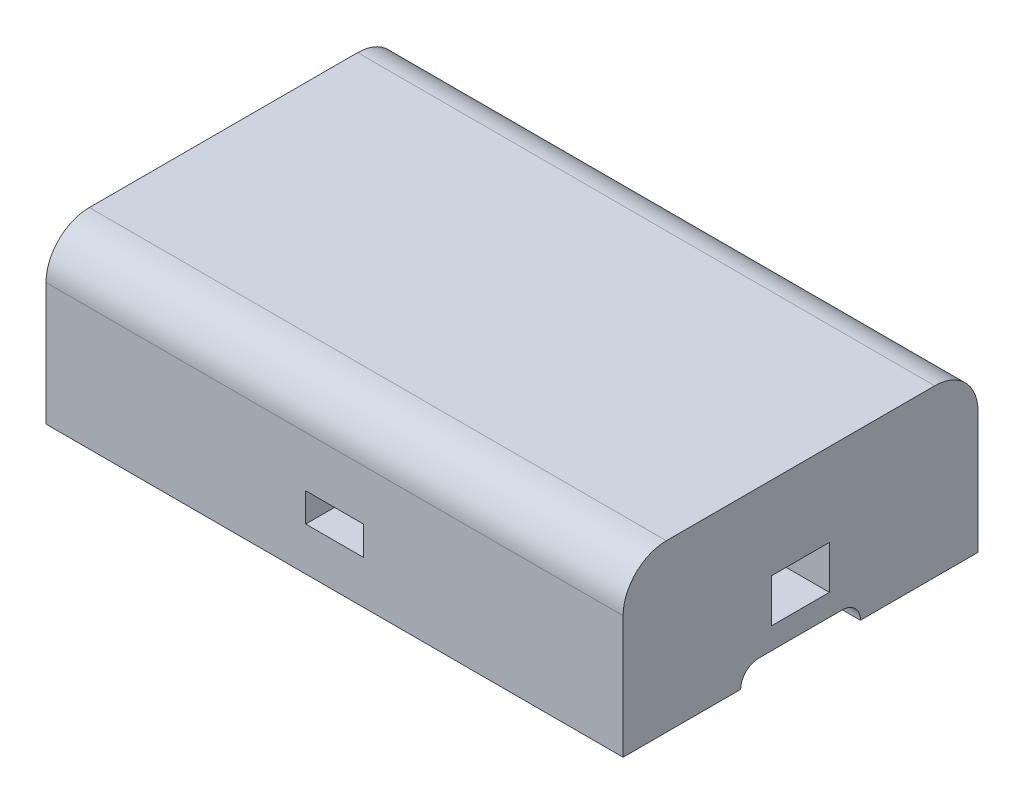
SolidWorks part; units mm, degrees
ref_plane "Front Plane" through (0, 0, 0) normal (0, 0, 1) x (1, 0, 0)
ref_plane "Top Plane" through (0, 0, 0) normal (0, 1, 0) x (1, 0, 0)
ref_plane "Right Plane" through (0, 0, 0) normal (1, 0, 0) x (0, 0, -1)
sketch "Sketch1" plane through (0, 0, 0) normal (0, 1, 0) x (1, 0, 0)
  line L1 (-17, 9.3) -> (17, 9.3)
  line L2 (-17, 9.3) -> (-17, -9.3)
  line L3 (-17, -9.3) -> (17, -9.3)
  line L4 (17, 9.3) -> (17, -9.3)
  line L5 (-17, 9.3) -> (17, -9.3) construction
  line L6 (-17, -9.3) -> (17, 9.3) construction
  line L7 (-20, 12.3) -> (20, 12.3)
  line L8 (-20, 12.3) -> (-20, -12.3)
  line L9 (-20, -12.3) -> (20, -12.3)
  line L10 (20, 12.3) -> (20, -12.3)
  line L11 (-20, 12.3) -> (20, -12.3) construction
  line L12 (-20, -12.3) -> (20, 12.3) construction
  point P0 (0, 0)
  point P6 (0, 0)
  dimension "D1" = 34
  dimension "D2" = 18.6
  dimension "D3" = 3
  dimension "D4" = 3
extrude "Boss-Extrude1" add sketch "Sketch1" along normal blind 14
ref_plane "Plane1" through (0, 5.5, 0) normal (0, -1, 0) x (-1, 0, 0)
sketch "Sketch3" plane through (20, 0, 0) normal (1, 0, 0) x (0, 0, -1)
  line L0 (-13.53, 5.5) -> (13.53, 5.5) construction
  line L1 (-2.9, 5.5) -> (2.9, 5.5) construction
  line L2 (-2.9, 6.75) -> (2.9, 6.75)
  line L3 (-2.9, 4.25) -> (2.9, 4.25)
  line L5 (-4.15, 6.75) -> (4.15, 6.75)
  line L6 (-4.15, 6.75) -> (-4.15, 4.25)
  line L7 (-4.15, 4.25) -> (4.15, 4.25)
  line L8 (4.15, 6.75) -> (4.15, 4.25)
  line L9 (-4.15, 6.75) -> (4.15, 4.25) construction
  line L10 (-4.15, 4.25) -> (4.15, 6.75) construction
  arc A0 (-2.9, 6.75) -> (-2.9, 4.25) centre (-2.9, 5.5) ccw
  arc A1 (2.9, 4.25) -> (2.9, 6.75) centre (2.9, 5.5) ccw
  point P4 (0, 5.5)
  point P9 (0, 5.5)
  dimension "D4" = 1.25
  dimension "D1" = 8.3
  dimension "D2" = 2.5
  dimension "D3" = 0
  dimension "D5" = 0
extrude "Cut-Extrude1" cut sketch "Sketch3" against normal blind 10 contours A1 L2 A0 L3 region at (20, 5.5, 0)
split "Split1" trim tools "Plane1" bodies to split 102 resulting bodies 103 104
sketch "Sketch5" plane through (20, 0, 0) normal (1, 0, 0) x (0, 0, -1)
  line L0 (-2.9, 6.75) -> (2.9, 6.75) construction
  line L1 (-2, 11.25) -> (2, 11.25)
  line L2 (-2, 11.25) -> (-2, 8.25)
  line L3 (-2, 8.25) -> (2, 8.25)
  line L4 (2, 11.25) -> (2, 8.25)
  line L5 (-2, 11.25) -> (2, 8.25) construction
  line L6 (-2, 8.25) -> (2, 11.25) construction
  point P0 (0, 9.75)
  dimension "D1" = 3
  dimension "D2" = 4
  dimension "D3" = 0
  dimension "D4" = 1.5
extrude "Cut-Extrude2" cut sketch "Sketch5" against normal blind 10
sketch "Sketch6" plane through (20, 0, 0) normal (1, 0, 0) x (0, 0, -1)
  line L0 (-12.3, 14) -> (12.3, 14) construction
  line L1 (-9.3, 17) -> (9.3, 17)
  line L2 (-12.3, 14) -> (12.3, 14)
  arc A0 (-12.3, 14) -> (-9.3, 17) centre (-9.3, 14) cw
  arc A1 (12.3, 14) -> (9.3, 17) centre (9.3, 14) ccw
  dimension "D3" = 3
  dimension "D1" = 3
  dimension "D2" = 3
extrude "Boss-Extrude2" add sketch "Sketch6" against normal blind 40 contours L1 A1 L2 A0
sketch "Sketch7" plane through (-20, 0, 0) normal (-1, 0, 0) x (0, 0, 1)
  line L0 (-12.3, 0) -> (12.3, 0) construction
  line L1 (12.3, 5.5) -> (12.3, 0) construction
  line L2 (-12.3, 5.5) -> (-12.3, 0) construction
  line L3 (-9.3, -3) -> (9.3, -3)
  line L4 (12.3, 0) -> (-12.3, 0)
  arc A0 (-12.3, 0) -> (-9.3, -3) centre (-9.3, 0) ccw
  arc A1 (12.3, 0) -> (9.3, -3) centre (9.3, 0) cw
  dimension "D1" = 3
  dimension "D2" = 3
  dimension "D3" = 0
  dimension "D4" = 0
extrude "Boss-Extrude3" add sketch "Sketch7" against normal blind 40
sketch "Sketch8" plane through (0, 0, 12.3) normal (0, 0, 1) x (1, 0, 0)
  line L1 (2, 0.5) -> (-2, 0.5)
  line L2 (2, 0.5) -> (2, 12.5)
  line L3 (2, 12.5) -> (-2, 12.5)
  line L4 (-2, 0.5) -> (-2, 12.5)
  line L5 (2, 0.5) -> (-2, 12.5) construction
  line L6 (2, 12.5) -> (-2, 0.5) construction
  line L7 (20, 5.5) -> (-20, 5.5) construction
  point P0 (0, 6.5)
  point P7 (0, 5.5)
  point P8 (0, 0)
  dimension "D1" = 4
  dimension "D2" = 12
  dimension "D3" = 5
extrude "Boss-Extrude4" add sketch "Sketch8" along normal blind 1
fillet "Fillet4" radius 21 1 edges at (0, 0.5, 13.3)
sketch "Sketch10" plane through (0, 0, 12.3) normal (0, 0, -1) x (-1, 0, 0)
  line L0 (2, 12.5) -> (2, 5.5) construction
  line L1 (-2, 10.5) -> (2, 10.5)
  line L2 (-2, 10.5) -> (-2, 8.5)
  line L3 (-2, 8.5) -> (2, 8.5)
  line L4 (2, 10.5) -> (2, 8.5)
  line L5 (-2, 10.5) -> (2, 8.5) construction
  line L6 (-2, 8.5) -> (2, 10.5) construction
  line L8 (-2, 12.5) -> (2, 12.5) construction
  point P0 (0, 9.5)
  dimension "D1" = 2
  dimension "D2" = 2
extrude "Boss-Extrude6" add sketch "Sketch10" along normal blind 1
sketch "Sketch13" plane through (0, 0, -12.3) normal (0, 0, -1) x (-1, 0, 0)
  line L0 (20, 5.5) -> (-20, 5.5) construction
  line L1 (-13, 5.5) -> (-11, 5.5)
  line L2 (-13, 5.5) -> (-13, 8.5)
  line L3 (-13, 8.5) -> (-11, 8.5)
  line L4 (-11, 5.5) -> (-11, 8.5)
  line L5 (0, 0) -> (0, -9.2638) construction
  line L6 (11, 5.5) -> (11, 8.5)
  line L7 (13, 8.5) -> (11, 8.5)
  line L8 (13, 5.5) -> (13, 8.5)
  line L9 (13, 5.5) -> (11, 5.5)
  line L10 (-20, 5.5) -> (-20, 0) construction
  dimension "D1" = 3
  dimension "D2" = 2
  dimension "D3" = 7
extrude "Boss-Extrude7" add sketch "Sketch13" against normal blind 1
sketch "Sketch14" plane through (0, 0, -11.3) normal (0, 0, 1) x (1, 0, 0)
  line L0 (-11, 8.5) -> (-11, 5.5) construction
  line L1 (-13, 8.5) -> (-11, 8.5)
  line L2 (-13, 8.5) -> (-13, 7)
  line L3 (-13, 7) -> (-11, 7)
  line L4 (-11, 8.5) -> (-11, 7)
  line L5 (13, 8.5) -> (13, 5.5) construction
  line L6 (11, 8.5) -> (13, 8.5)
  line L7 (11, 8.5) -> (11, 7)
  line L8 (11, 7) -> (13, 7)
  line L9 (13, 8.5) -> (13, 7)
  dimension "D1" = 1.5
  dimension "D2" = 1.5
extrude "Boss-Extrude9" add sketch "Sketch14" along normal blind 1 contours L8 L9 L6 L7
extrude "Boss-Extrude10" add sketch "Sketch14<4>" along normal blind 1
sketch "Sketch14<4>" plane through (0, 0, -11.3) normal (0, 0, 1) x (1, 0, 0) same geometry as "Sketch14"
sketch "Sketch15" plane through (13, 0, 0) normal (1, 0, 0) x (0, 0, -1)
  line L0 (10.3, 7) -> (11.3, 8.5)
  line L1 (10.3, 8.5) -> (12.3, 8.5) construction
  line L2 (11.3, 8.5) -> (10.3, 8.5)
  line L3 (10.3, 8.5) -> (10.3, 7)
extrude "Cut-Extrude5" cut sketch "Sketch15" against normal blind 28
sketch "Sketch16" plane through (2, 0, 0) normal (1, 0, 0) x (0, 0, -1)
  line L0 (-13.3, 12.5) -> (-12.3, 10.5)
  line L1 (-12.3, 10.5) -> (-12.3, 12.5)
  line L2 (-12.3, 12.5) -> (-13.3, 12.5)
extrude "Cut-Extrude6" cut sketch "Sketch16" against normal blind 28
fillet "Fillet7" radius 0.25 1 edges at (0, 12.5, 13.3)
sketch "Sketch18" plane through (0, 0, 0) normal (0, 1, 0) x (1, 0, 0)
  line L1 (-17, 9.3) -> (17, 9.3)
  line L2 (-17, 9.3) -> (-17, -9.3)
  line L3 (-17, -9.3) -> (17, -9.3)
  line L4 (17, 9.3) -> (17, -9.3)
extrude "Boss-Extrude11" add sketch "Sketch18" along normal blind 1.25
sketch "Sketch19" plane through (-2, 0, 0) normal (-1, 0, 0) x (0, 0, 1)
  line L0 (12.3, 10.5) -> (11.3, 8.5)
  line L1 (11.3, 8.5) -> (11.3, 10.5)
  line L2 (11.3, 10.5) -> (12.3, 10.5)
extrude "Cut-Extrude7" cut sketch "Sketch19" against normal blind 5.25
combine bodies "Combine3" operation type subtract main body 106 bodies to subtract 122
sketch "Sketch20" plane through (0, 0, 12.3) normal (0, 0, 1) x (1, 0, 0)
  line L1 (-2, 10.5) -> (2, 10.5)
  line L2 (-2, 10.5) -> (-2, 8.5)
  line L3 (-2, 8.5) -> (2, 8.5)
  line L4 (2, 10.5) -> (2, 8.5)
extrude "Cut-Extrude8" cut sketch "Sketch20" against normal blind 5.25
sketch "Sketch21" plane through (0, 0, -12.3) normal (0, 0, -1) x (-1, 0, 0)
  line L0 (-11, 5.5) -> (-11, 8.5) construction
  line L1 (-13, 8.5) -> (-11, 8.5)
  line L2 (-13, 8.5) -> (-13, 7)
  line L3 (-13, 7) -> (-11, 7)
  line L4 (-11, 8.5) -> (-11, 7)
  line L5 (13, 5.5) -> (13, 8.5) construction
  line L6 (11, 8.5) -> (13, 8.5)
  line L7 (11, 8.5) -> (11, 7)
  line L8 (11, 7) -> (13, 7)
  line L9 (13, 8.5) -> (13, 7)
extrude "Cut-Extrude9" cut sketch "Sketch21" against normal blind 5.25
